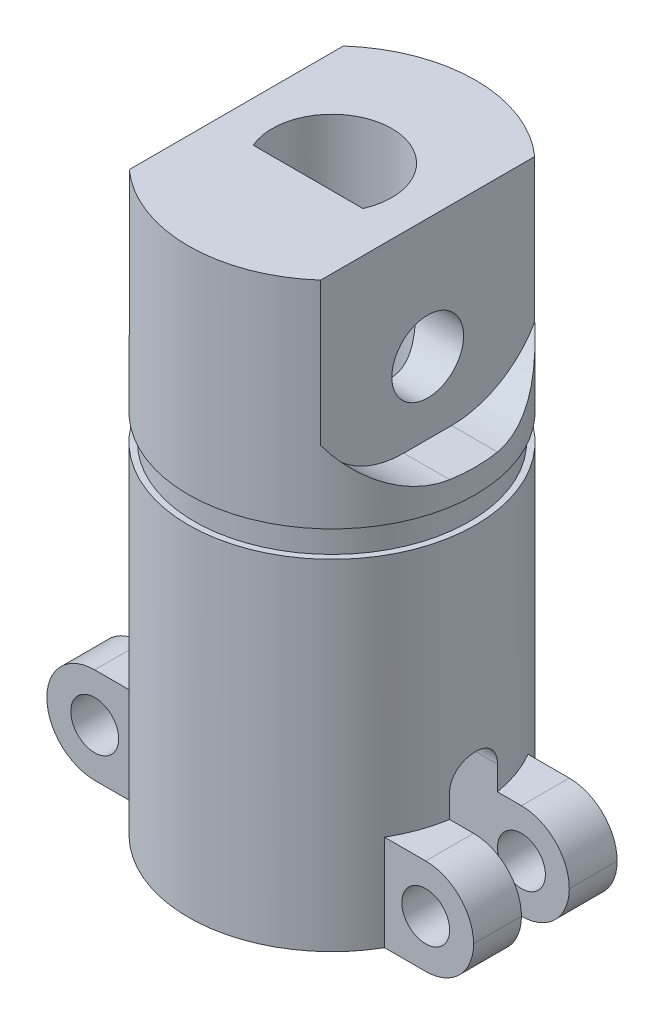
SolidWorks part; units mm, degrees
material "Polyetheretherketone (PEEK)"
ref_plane "Front Plane" through (0, 0, 0) normal (0, 0, 1) x (1, 0, 0)
ref_plane "Top Plane" through (0, 0, 0) normal (0, 1, 0) x (1, 0, 0)
ref_plane "Right Plane" through (0, 0, 0) normal (1, 0, 0) x (0, 0, -1)
sketch "Sketch2" plane through (0, 0, 0) normal (0, 0, 1) x (1, 0, 0)
  line L0 (0, 0) -> (0, 26.1) construction
  line L19 (0, 26.1) -> (-6, 26.1)
  line L20 (-6, 26.1) -> (-6, 17.1)
  line L21 (-6, 17.1) -> (-5.75, 17.1)
  line L22 (-5.75, 17.1) -> (-5.75, 16)
  line L23 (-5.75, 16) -> (-6, 16)
  line L24 (-6, 16) -> (-6, 4)
  line L25 (-6, 4) -> (-8, 4)
  line L26 (-8, 4) -> (-8, 0)
  line L27 (-8, 0) -> (-7, 0)
  line L28 (-7, 0) -> (-7, 1.8)
  line L29 (-7, 1.8) -> (0, 1.8)
  line L31 (0, 1.8) -> (0, 26.1)
  line L40 (-6, 4) -> (-10.5, 4) construction
  line L41 (-6, 4) -> (-6, 9) construction
  line L42 (-6, 9) -> (-10.5, 9) construction
  line L43 (-10.5, 4) -> (-10.5, 9) construction
  line L44 (-6, 16) -> (-10.5, 16) construction
  line L45 (-6, 16) -> (-6, 11) construction
  line L46 (-6, 11) -> (-10.5, 11) construction
  line L47 (-10.5, 16) -> (-10.5, 11) construction
  dimension "D1" = 12
  dimension "D2" = 10.5
  dimension "D3" = 5
  dimension "D4" = 5
  dimension "D5" = 16
  dimension "D6" = 14
  dimension "D8" = 1.8
  dimension "D9" = 1.1
  dimension "D10" = 11.5
  dimension "D11" = 9
  dimension "D12" = 4
  dimension "D13" = 12
revolve "Revolve1" add sketch "Sketch2" angle 360 about L0
ref_plane "Plane1" through (-6, 0, 0) normal (-1, 0, 0) x (0, 0, 1)
sketch "Sketch3" plane through (-6, 0, 0) normal (-1, 0, 0) x (0, 0, 1)
  line L0 (0, 26.1) -> (0, 9.9472) construction
  line L1 (6, 26.1) -> (-6, 26.1) construction
  line L2 (9, 26.1) -> (-9, 26.1)
  line L3 (-1, 18.1) -> (1, 18.1)
  arc A0 (-9, 26.1) -> (-5, 22.1) centre (-9, 22.1) cw
  arc A1 (-5, 22.1) -> (-1, 18.1) centre (-1, 22.1) ccw
  arc A2 (9, 26.1) -> (5, 22.1) centre (9, 22.1) ccw
  arc A3 (5, 22.1) -> (1, 18.1) centre (1, 22.1) cw
  point P13 (0, 18.1)
  dimension "D1" = 1
  dimension "D2" = 8
  dimension "D3" = 4
  dimension "D4" = 4
  dimension "D5" = 8
extrude "Cut-Extrude2" cut sketch "Sketch3" against normal blind 2 contours A0 A1 L3 A3 A2 L2
mirror "Mirror1" about plane through (0, 0, 0) normal (1, 0, 0) of "Cut-Extrude2"
sketch "Sketch4" plane through (-4, 0, 0) normal (-1, 0, 0) x (0, 0, 1)
  line L0 (1, 18.1) -> (-1, 18.1) construction
  circle A0 centre (0, 21.1) radius 1.5
  point P5 (0, 18.1)
  dimension "D1" = 3
  dimension "D2" = 3
extrude "Cut-Extrude3" cut sketch "Sketch4" against normal through all contours A0
sketch "Sketch5" plane through (0, 1.8, 0) normal (0, -1, 0) x (1, 0, 0)
  line L0 (-2.2913, 1) -> (2.2913, 1)
  circle A0 centre (0, 0) radius 2.5
  dimension "D1" = 5
  dimension "D2" = 1
extrude "Cut-Extrude4" cut sketch "Sketch5" against normal through all contours L0 A0 region at (0, 1.8, -0.5463)
sketch "Sketch6" plane through (0, 4, 0) normal (0, 1, 0) x (1, 0, 0)
  circle A0 centre (0, 0) radius 6
  circle A1 centre (0, 0) radius 8
  circle A2 centre (0, 0) radius 8
  dimension "D1" = 0
extrude "Cut-Extrude5" cut sketch "Sketch6" against normal blind 10
ref_plane "Plane2" through (6, 0, 0) normal (1, 0, 0) x (0, 0, -1)
sketch "Sketch7" plane through (6, 0, 0) normal (1, 0, 0) x (0, 0, -1)
  line L0 (-1, 1.8) -> (2.5, 1.8) construction
  line L1 (-1, 1.8) -> (2.5, 1.8) construction
  line L2 (-1, 1.8) -> (-1, 6.8)
  line L3 (1, 6.8) -> (1, 1.8)
  line L4 (1, 1.8) -> (-1, 1.8)
  arc A0 (-1, 6.8) -> (1, 6.8) centre (0, 6.8) cw
  dimension "D1" = 1
  dimension "D2" = 5
extrude "Cut-Extrude6" cut sketch "Sketch7" against normal through all
sketch "Sketch8" plane through (0, 1.8, 0) normal (0, -1, 0) x (1, 0, 0)
  line L0 (5.9161, 1) -> (8.9161, 1)
  line L1 (8.9161, 1) -> (8.9161, 3)
  line L2 (8.9161, 3) -> (5.1962, 3)
  line L3 (0, 0) -> (0, -6.6764) construction
  line L4 (5.9161, -1) -> (8.9161, -1)
  line L5 (8.9161, -1) -> (8.9161, -3)
  line L6 (8.9161, -3) -> (5.1962, -3)
  line L7 (-8.9161, -3) -> (-5.1962, -3)
  line L8 (-8.9161, -1) -> (-8.9161, -3)
  line L9 (-5.9161, -1) -> (-8.9161, -1)
  line L10 (-8.9161, 3) -> (-5.1962, 3)
  line L11 (-8.9161, 1) -> (-8.9161, 3)
  line L12 (-5.9161, 1) -> (-8.9161, 1)
  arc A0 (5.9161, 1) -> (-5.9161, 1) centre (0, 0) ccw construction
  arc A1 (5.9161, 1) -> (5.1962, 3) centre (0, 0) ccw
  arc A2 (-5.9161, -1) -> (5.9161, -1) centre (0, 0) ccw construction
  arc A3 (-5.1962, -3) -> (-5.9161, -1) centre (0, 0) cw
  arc A4 (5.1962, -3) -> (5.9161, -1) centre (0, 0) ccw
  arc A5 (-5.9161, 1) -> (-5.1962, 3) centre (0, 0) cw
  point P2 (8.7541, -3.7002)
  point P10 (0, 0)
  point P11 (0, 0)
  point P14 (0, 0)
  point P17 (5.9161, -1)
  arc M10 (5.9161, 1) -> (-5.9161, 1) centre (0, 0) ccw
  dimension "D1" = 2
  dimension "D2" = 2
  dimension "D3" = 3
extrude "Boss-Extrude1" add sketch "Sketch8" against normal blind 4 contours L7 A3 L9 L8 | L12 L10 L11 M10 | L1 L2 L0 M10 | A4 L6 L5 L4 region at (7.2632, 1.8, 2.0362) region at (-7.2632, 1.8, 2.0362) region at (7.2632, 1.8, -2.0362) region at (-7.2632, 1.8, -2.0362)
sketch "Sketch9" plane through (0, 0, -3) normal (0, 0, -1) x (-1, 0, 0)
  line L0 (-8.9161, 5.8) -> (-8.9161, 1.8) construction
  line L1 (0, 0) -> (0, -2.3881) construction
  circle A0 centre (-6.9161, 3.8) radius 1
  circle A1 centre (6.9161, 3.8) radius 1
  point P4 (-8.9161, 3.8)
  dimension "D1" = 2
  dimension "D2" = 2
extrude "Cut-Extrude7" cut sketch "Sketch9" against normal through all
fillet "Fillet1" radius 2 8 edges at (-8.9161, 5.8, 2) (-8.9161, 1.8, 2) (-8.9161, 1.8, -2) (-8.9161, 5.8, -2) (8.9161, 1.8, 2) (8.9161, 5.8, 2) (8.9161, 1.8, -2) (8.9161, 5.8, -2)
